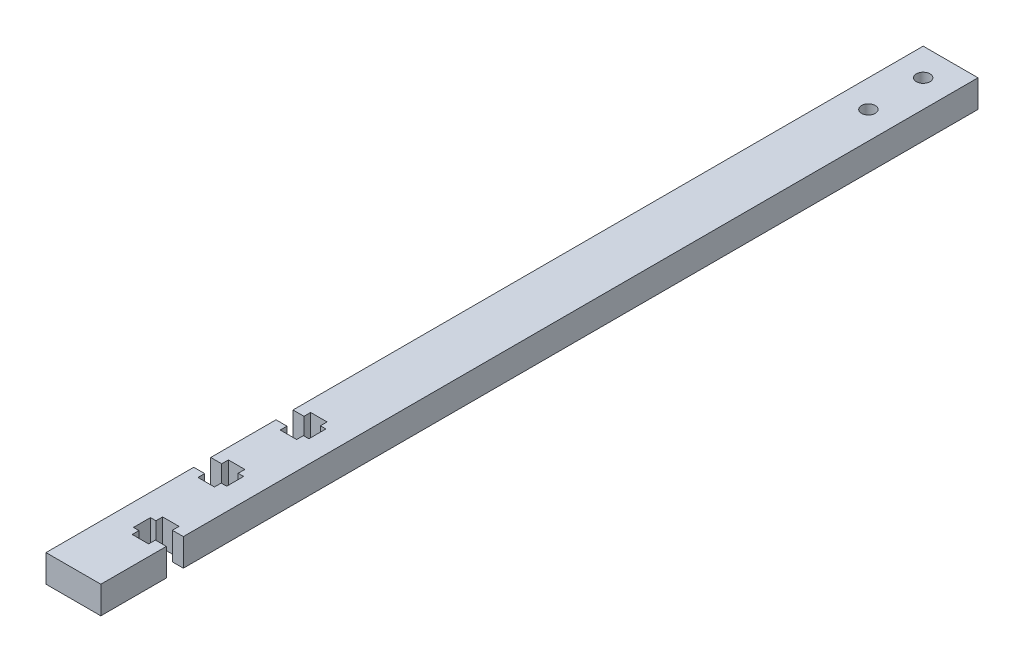
SolidWorks part; units mm, degrees
ref_plane "Plan de face" through (0, 0, 0) normal (0, 0, 1) x (1, 0, 0)
ref_plane "Plan de dessus" through (0, 0, 0) normal (0, 1, 0) x (1, 0, 0)
ref_plane "Plan de droite" through (0, 0, 0) normal (1, 0, 0) x (0, 0, -1)
sketch "Esquisse1" plane through (0, 0, 0) normal (0, 0, 1) x (1, 0, 0)
  line L1 (0, 0) -> (10, 0)
  line L2 (0, 0) -> (0, 5)
  line L3 (0, 5) -> (10, 5)
  line L4 (10, 0) -> (10, 5)
  dimension "D1" = 5
  dimension "D2" = 10
extrude "Boss.-Extru.1" add sketch "Esquisse1" along normal blind 160
sketch "Esquisse2" plane through (0, 5, 0) normal (0, 1, 0) x (1, 0, 0)
  line L0 (0, -160) -> (0, 0) construction
  line L1 (10, 0) -> (0, 0) construction
  line L2 (10, -160) -> (10, 0) construction
  line L3 (10, -144.95) -> (4, -144.95)
  line L4 (10, -144.95) -> (10, -148.05)
  line L5 (10, -148.05) -> (4, -148.05)
  line L6 (4, -144.95) -> (4, -148.05)
  line L7 (10, -160) -> (0, -160) construction
  line L8 (5, -143.73) -> (8, -143.73)
  line L9 (5, -143.73) -> (5, -149.28)
  line L10 (5, -149.28) -> (8, -149.28)
  line L11 (8, -143.73) -> (8, -149.28)
  line L12 (0, -118.05) -> (6, -118.05)
  line L13 (0, -118.05) -> (0, -114.95)
  line L14 (0, -114.95) -> (6, -114.95)
  line L15 (6, -118.05) -> (6, -114.95)
  line L16 (5, -119.28) -> (2, -119.28)
  line L17 (5, -119.28) -> (5, -113.73)
  line L18 (5, -113.73) -> (2, -113.73)
  line L19 (2, -119.28) -> (2, -113.73)
  line L20 (0, -133.05) -> (6, -133.05)
  line L21 (0, -133.05) -> (0, -129.95)
  line L22 (0, -129.95) -> (6, -129.95)
  line L23 (6, -133.05) -> (6, -129.95)
  line L24 (5, -134.28) -> (2, -134.28)
  line L25 (5, -134.28) -> (5, -128.73)
  line L26 (5, -128.73) -> (2, -128.73)
  line L27 (2, -134.28) -> (2, -128.73)
  circle A0 centre (5, -5) radius 1.25
  circle A1 centre (5, -15) radius 1.25
  point P29 (3, -118.05)
  point P38 (3, -133.05)
  line M2 (0, 0) -> (0, -160)
  line M4 (10, -160) -> (10, 0)
  dimension "D1" = 5
  dimension "D2" = 5
  dimension "D3" = 10
  dimension "D4" = 5
  dimension "D5" = 2.5
  dimension "D6" = 2.5
  dimension "D7" = 5.55
  dimension "D8" = 0
  dimension "D9" = 3.1
  dimension "D10" = 2
  dimension "D11" = 1
  dimension "D12" = 3
  dimension "D13" = 11.95
  dimension "D14" = 1.23
  dimension "D15" = 3.1
  dimension "D16" = 1.23
  dimension "D17" = 3.1
  dimension "D18" = 0
  dimension "D19" = 15
  dimension "D20" = 15
  dimension "D21" = 1.23
extrude "Enlèv. mat.-Extru.1" cut sketch "Esquisse2" against normal blind 10 contours L19 L12 L17 L14 | L12 L19 L14 M2 | L27 L20 L25 L22 | L20 L27 L22 M2 | L27 L22 L25 L26 | L25 L20 L23 L22 | L27 L24 L25 L20 | L3 L11 L5 M4 | L11 L3 L9 L5 | L11 L8 L9 L3 | L9 L3 L6 L5 | L11 L5 L9 L10 | A0 | A1 | L18 L19 L16 L17 | L15 L14 L13 L12 region at (9, 5, 146.5) region at (6.5, 5, 146.5) region at (6.5, 5, 144.34) region at (4.5, 5, 146.5) region at (6.5, 5, 148.665) region at (1, 5, 116.5) region at (1, 5, 131.5) region at (3.5, 5, 116.5) region at (3.5, 5, 129.34) region at (3.5, 5, 131.5) region at (3.5, 5, 133.665) region at (5.5, 5, 131.5) region at (5, 5, 5) region at (5, 5, 15)
